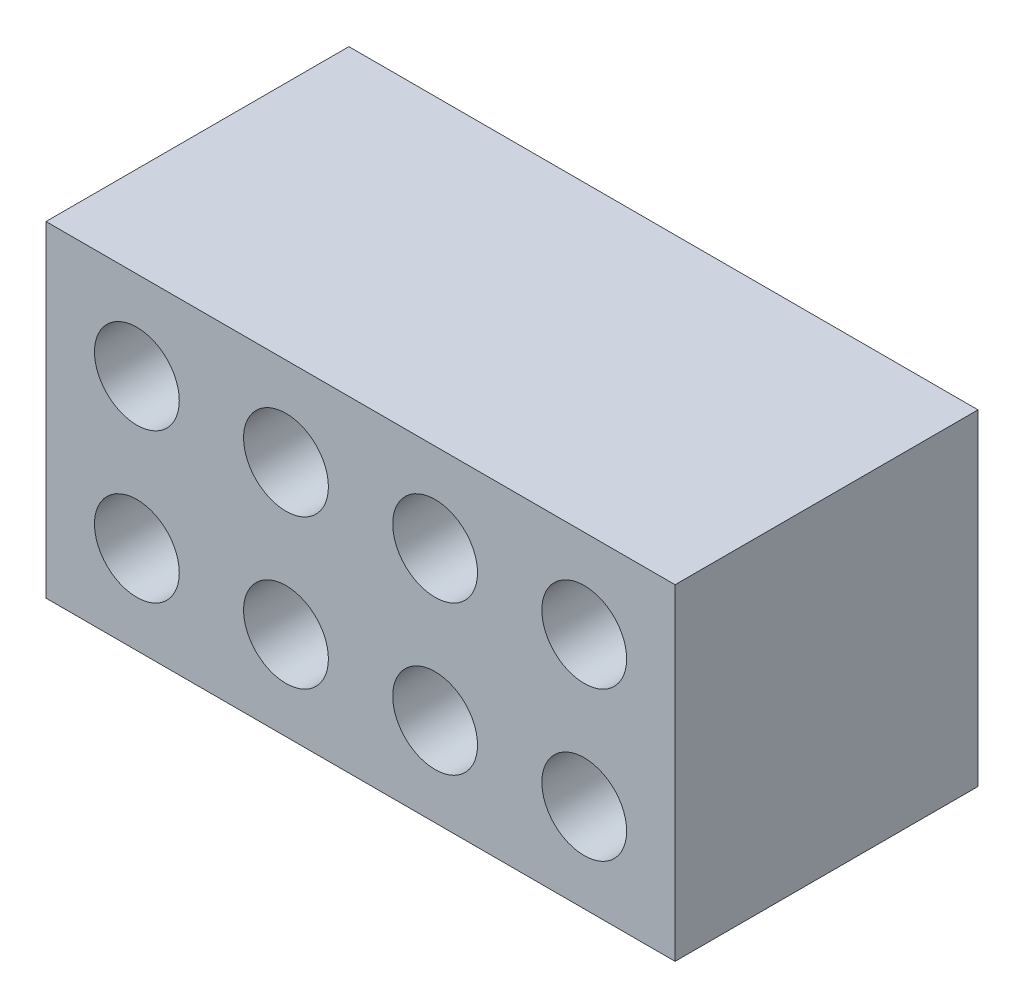
SolidWorks part; units mm, degrees
ref_plane "前视基准面" through (0, 0, 0) normal (0, 0, 1) x (1, 0, 0)
ref_plane "上视基准面" through (0, 0, 0) normal (0, 1, 0) x (1, 0, 0)
ref_plane "右视基准面" through (0, 0, 0) normal (1, 0, 0) x (0, 0, -1)
other "Configuration Table"
sketch "Sketch1" plane through (0, 0, 0) normal (0, 0, 1) x (1, 0, 0)
  line L1 (-67.5, -35) -> (67.5, -35)
  line L2 (-67.5, -35) -> (-67.5, 35)
  line L3 (-67.5, 35) -> (67.5, 35)
  line L4 (67.5, -35) -> (67.5, 35)
  line L5 (-67.5, -35) -> (67.5, 35) construction
  line L6 (-67.5, 35) -> (67.5, -35) construction
  point P0 (0, 0)
extrude "Boss-Extrude1" add sketch "Sketch1" along normal blind 65
ref_plane "Plane1" through (0, 0, 65) normal (0, 0, 1) x (1, 0, 0)
sketch "Sketch2" plane through (0, 0, 65) normal (0, 0, 1) x (1, 0, 0)
  circle A0 centre (-48, -16) radius 9.1
  circle A1 centre (-16, -16) radius 9.1
  circle A2 centre (16, -16) radius 9.1
  circle A3 centre (48, -16) radius 9.1
  circle A4 centre (-48, 16) radius 9.1
  circle A5 centre (-16, 16) radius 9.1
  circle A6 centre (16, 16) radius 9.1
  circle A7 centre (48, 16) radius 9.1
extrude "Cut-Extrude1" cut sketch "Sketch2" against normal blind 66
ref_plane "face_bottom_support" through (0, 0, 0) normal (0, 0, 1) x (1, 0, 0)
ref_plane "face_top_open" through (0, 0, 65) normal (0, 0, 1) x (1, 0, 0)
sketch3d "3DSketch1"
  line L0 (-48, -16, 0) -> (-48, -16, 65) construction
ref_axis "axis_cell_1_1" through (-48, -16, 0) along (0, 0, 1)
sketch3d "3DSketch2"
  line L0 (-16, -16, 0) -> (-16, -16, 65) construction
ref_axis "axis_cell_1_2" through (-16, -16, 0) along (0, 0, 1)
sketch3d "3DSketch3"
  line L0 (16, -16, 0) -> (16, -16, 65) construction
ref_axis "axis_cell_1_3" through (16, -16, 0) along (0, 0, 1)
sketch3d "3DSketch4"
  line L0 (48, -16, 0) -> (48, -16, 65) construction
ref_axis "axis_cell_1_4" through (48, -16, 0) along (0, 0, 1)
sketch3d "3DSketch5"
  line L0 (-48, 16, 0) -> (-48, 16, 65) construction
ref_axis "axis_cell_2_1" through (-48, 16, 0) along (0, 0, 1)
sketch3d "3DSketch6"
  line L0 (-16, 16, 0) -> (-16, 16, 65) construction
ref_axis "axis_cell_2_2" through (-16, 16, 0) along (0, 0, 1)
sketch3d "3DSketch7"
  line L0 (16, 16, 0) -> (16, 16, 65) construction
ref_axis "axis_cell_2_3" through (16, 16, 0) along (0, 0, 1)
sketch3d "3DSketch8"
  line L0 (48, 16, 0) -> (48, 16, 65) construction
ref_axis "axis_cell_2_4" through (48, 16, 0) along (0, 0, 1)
